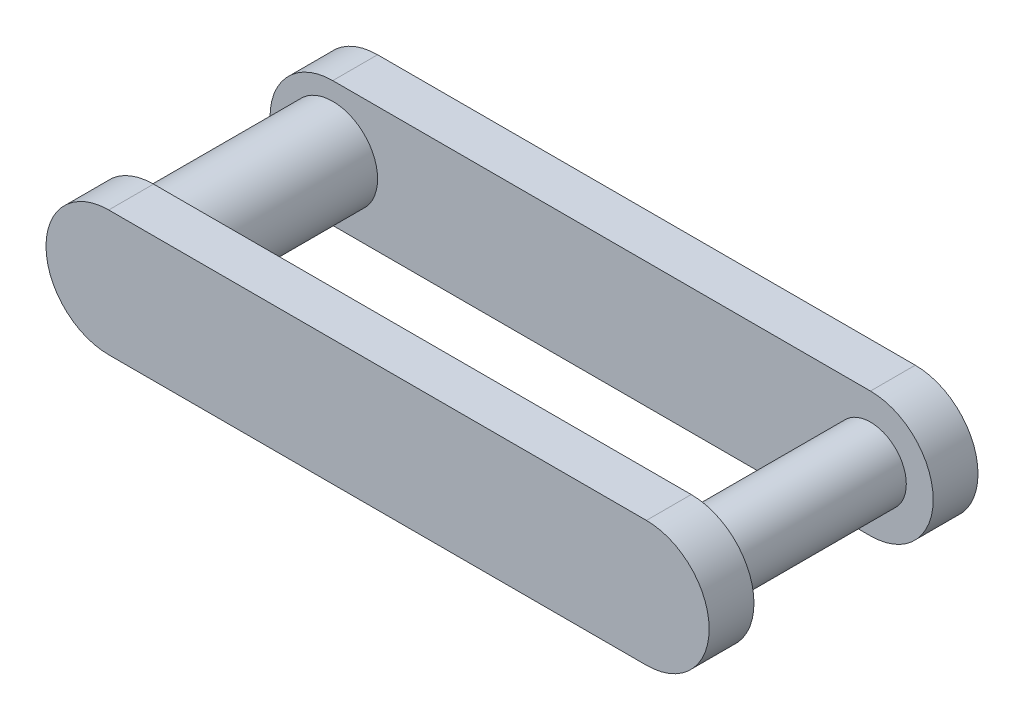
SolidWorks part; units mm, degrees
ref_plane "Alzado" through (0, 0, 0) normal (0, 0, 1) x (1, 0, 0)
ref_plane "Planta" through (0, 0, 0) normal (0, 1, 0) x (1, 0, 0)
ref_plane "Vista lateral" through (0, 0, 0) normal (1, 0, 0) x (0, 0, -1)
sketch "Croquis1" plane through (0, 0, 0) normal (0, 0, 1) x (1, 0, 0)
  line L0 (-53.9188, 0) -> (53.9188, 0) construction
  line L1 (-30, 0) -> (30, 0) construction
  line L2 (-30, 0) -> (30, 0) construction
  line L3 (-30, 12) -> (30, 12)
  line L4 (-30, -12) -> (30, -12)
  circle A0 centre (-30, 0) radius 5
  arc A1 (-30, 12) -> (-30, -12) centre (-30, 0) ccw
  arc A2 (30, -12) -> (30, 12) centre (30, 0) ccw
  circle A3 centre (30, 0) radius 4
  point P4 (0, 0)
  point P8 (0, 0)
  point P9 (0, 0)
  dimension "D2" = 10
  dimension "D3" = 12
  dimension "D4" = 8
  dimension "D1" = 60
extrude "Saliente-Extruir1" add sketch "Croquis1" along normal blind 10 and the other way blind 10 contours A0 | A3
sketch "Croquis2" plane through (0, 0, 10) normal (0, 0, 1) x (1, 0, 0)
  line L0 (-30, 0) -> (30, 0) construction
  line L1 (-30, 7) -> (30, 7)
  line L2 (-30, -7) -> (30, -7)
  arc A0 (-30, 7) -> (-30, -7) centre (-30, 0) ccw
  arc A1 (30, -7) -> (30, 7) centre (30, 0) ccw
  point P4 (0, 0)
  dimension "D1" = 7
extrude "Saliente-Extruir2" add sketch "Croquis2" along normal blind 5
mirror "Simetría1" about plane through (0, 0, 0) normal (0, 0, 1) of "Saliente-Extruir2"
